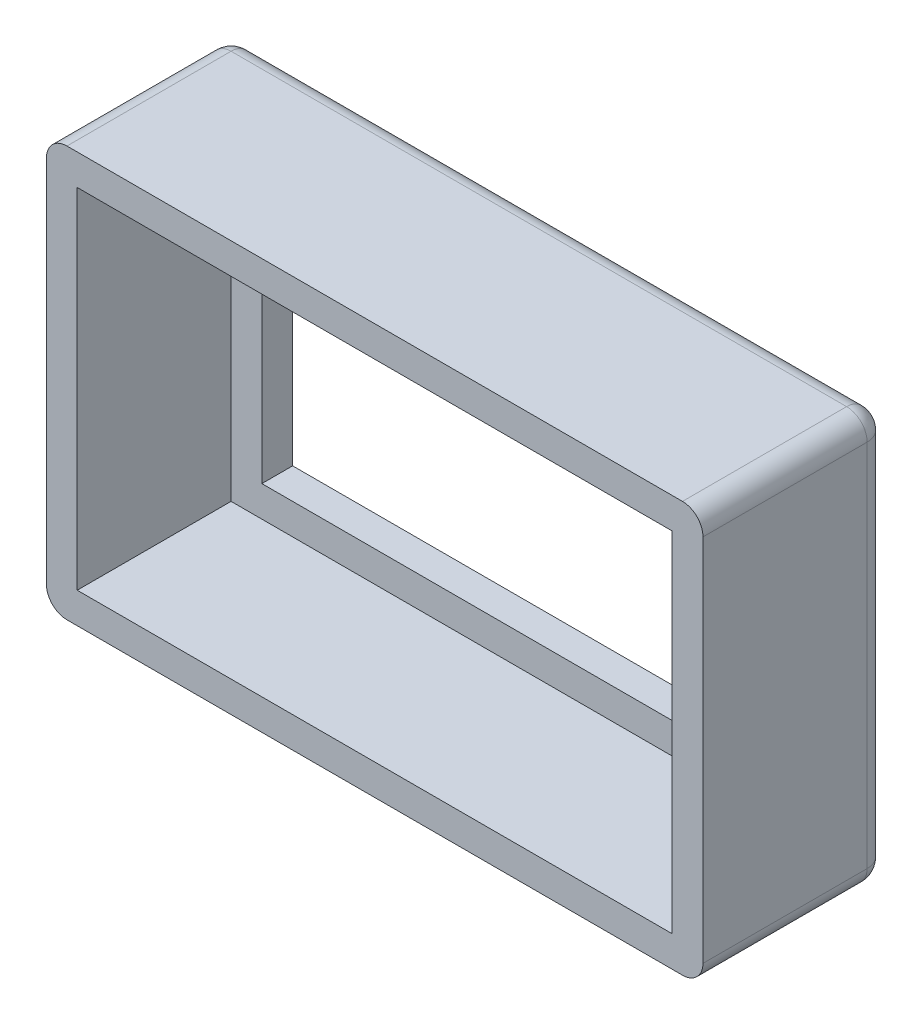
SolidWorks part; units mm, degrees
ref_plane "Front Plane" through (0, 0, 0) normal (0, 0, 1) x (1, 0, 0)
ref_plane "Top Plane" through (0, 0, 0) normal (0, 1, 0) x (1, 0, 0)
ref_plane "Right Plane" through (0, 0, 0) normal (1, 0, 0) x (0, 0, -1)
sketch "Sketch1" plane through (0, 0, 0) normal (0, 0, 1) x (1, 0, 0)
  line L8 (30.988, -57.912) -> (14.732, -57.912)
  line L9 (14.732, -57.912) -> (14.732, -68.072)
  line L10 (14.732, -68.072) -> (30.988, -68.072)
  line L11 (30.988, -68.072) -> (30.988, -57.912)
  line L17 (16.256, -66.548) -> (29.464, -66.548)
  line L18 (16.256, -59.436) -> (16.256, -66.548)
  line L19 (29.464, -59.436) -> (16.256, -59.436)
  line L20 (29.464, -66.548) -> (29.464, -59.436)
extrude "Boss-Extrude1" add sketch "Sketch1" against normal blind 4.572
sketch "Sketch2" plane through (0, 0, 0) normal (0, 0, 1) x (1, 0, 0)
  line L0 (16.256, -59.436) -> (14.732, -57.912) construction
  line L1 (29.464, -66.548) -> (30.988, -68.072) construction
  line L3 (15.494, -58.674) -> (30.226, -58.674)
  line L4 (15.494, -58.674) -> (15.494, -67.31)
  line L5 (15.494, -67.31) -> (30.226, -67.31)
  line L6 (30.226, -58.674) -> (30.226, -67.31)
  line L7 (15.494, -58.674) -> (30.226, -67.31) construction
  line L8 (15.494, -67.31) -> (30.226, -58.674) construction
  point P12 (22.86, -62.992)
extrude "Cut-Extrude1" cut sketch "Sketch2" against normal offset from surface (3.81 mm away) 0.762 up to face at (22.86, -62.992, -4.572)
fillet "Fillet1" radius 0.508 8 edges at (30.988, -62.992, -4.572) (22.86, -57.912, -4.572) (14.732, -62.992, -4.572) (22.86, -68.072, -4.572) (14.732, -57.912, -2.286) (30.988, -57.912, -2.286) (14.732, -68.072, -2.286) (30.988, -68.072, -2.286)
